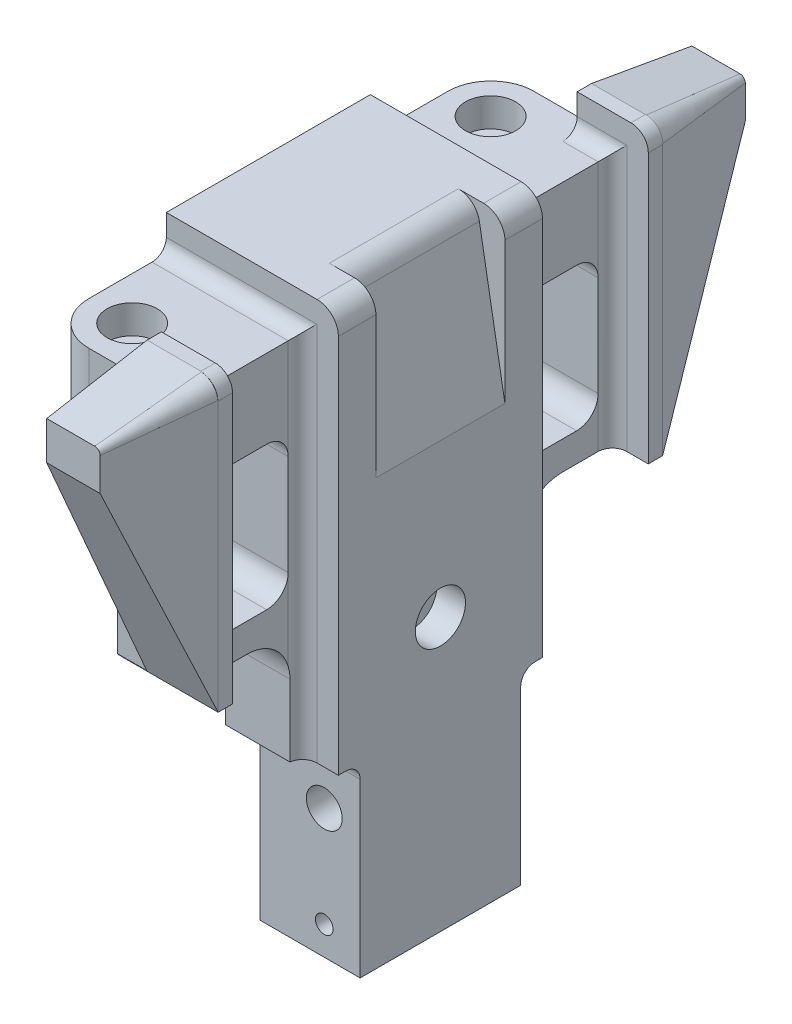
SolidWorks part; units mm, degrees
material "Nylon 101"
ref_plane "Front Plane" through (0, 0, 0) normal (0, 0, 1) x (1, 0, 0)
ref_plane "Top Plane" through (0, 0, 0) normal (0, 1, 0) x (1, 0, 0)
ref_plane "Right Plane" through (0, 0, 0) normal (1, 0, 0) x (0, 0, -1)
sketch "Sketch1" plane through (0, 0, 0) normal (0, 0, 1) x (1, 0, 0)
  line L1 (-19.05, -65.0875) -> (19.05, -65.0875)
  line L2 (-19.05, -65.0875) -> (-19.05, 65.0875)
  line L3 (-19.05, 65.0875) -> (19.05, 65.0875)
  line L4 (19.05, -65.0875) -> (19.05, 65.0875)
  line L5 (-19.05, -65.0875) -> (19.05, 65.0875) construction
  line L6 (-19.05, 65.0875) -> (19.05, -65.0875) construction
  point P0 (0, 0)
  dimension "D1" = 38.1
  dimension "D2" = 130.175
extrude "Boss-Extrude1" add sketch "Sketch1" against normal blind 71.4375
sketch "Sketch2" plane through (19.05, 0, 0) normal (1, 0, 0) x (0, 0, -1)
  line L0 (71.4375, -65.0875) -> (71.4375, 65.0875) construction
  line L1 (71.4375, 1.5875) -> (34.925, 1.5875)
  line L2 (71.4375, 1.5875) -> (71.4375, -65.0875)
  line L3 (71.4375, -65.0875) -> (25.4, -65.0875)
  line L4 (25.4, -7.9375) -> (25.4, -65.0875)
  line L5 (71.4375, -65.0875) -> (0, -65.0875) construction
  line L6 (71.4375, 65.0875) -> (0, 65.0875) construction
  line L7 (0, -65.0875) -> (0, 65.0875) construction
  arc A0 (25.4, -7.9375) -> (34.925, 1.5875) centre (34.925, -7.9375) cw
  dimension "D3" = 9.525
  dimension "D1" = 63.5
  dimension "D2" = 25.4
extrude "Cut-Extrude1" cut sketch "Sketch2" against normal through all
sketch "Sketch3" plane through (19.05, 0, 0) normal (1, 0, 0) x (0, 0, -1)
  line L0 (25.4, -7.9375) -> (25.4, -65.0875) construction
  line L1 (25.4, -23.8125) -> (20.955, -23.8125)
  line L2 (25.4, -23.8125) -> (25.4, -65.0875)
  line L3 (25.4, -65.0875) -> (17.78, -65.0875)
  line L4 (17.78, -26.9875) -> (17.78, -65.0875)
  line L5 (25.4, -65.0875) -> (0, -65.0875) construction
  arc A0 (17.78, -26.9875) -> (20.955, -23.8125) centre (20.955, -26.9875) cw
  point P10 (17.78, -23.8125)
  dimension "D2" = 3.175
  dimension "D1" = 7.62
  dimension "D3" = 41.275
extrude "Cut-Extrude2" cut sketch "Sketch3" against normal through all
sketch "Sketch4" plane through (19.05, 0, 0) normal (1, 0, 0) x (0, 0, -1)
  line L0 (71.4375, 65.0875) -> (0, 65.0875) construction
  line L1 (22.5933, 65.0875) -> (46.0375, 65.0875)
  line L2 (22.5933, 65.0875) -> (22.5933, 60.325)
  line L3 (25.7683, 57.15) -> (42.8625, 57.15)
  line L4 (46.0375, 65.0875) -> (46.0375, 60.325)
  line L7 (71.4375, 1.5875) -> (71.4375, 65.0875) construction
  arc A0 (46.0375, 60.325) -> (42.8625, 57.15) centre (42.8625, 60.325) cw
  arc A1 (25.7683, 57.15) -> (22.5933, 60.325) centre (25.7683, 60.325) cw
  dimension "D4" = 3.175
  dimension "D1" = 25.4
  dimension "D2" = 23.4442
  dimension "D3" = 7.9375
extrude "Cut-Extrude3" cut sketch "Sketch4" against normal through all
sketch "Sketch5" plane through (0, 57.15, 0) normal (0, 1, 0) x (1, 0, 0)
  line L0 (-19.05, 22.5933) -> (19.05, 22.5933) construction
  line L1 (19.05, 46.0375) -> (14.2875, 46.0375)
  line L2 (19.05, 46.0375) -> (19.05, 22.5933)
  line L3 (19.05, 22.5933) -> (14.2875, 22.5933)
  line L4 (11.1125, 42.8625) -> (11.1125, 25.7683)
  arc A0 (14.2875, 22.5933) -> (11.1125, 25.7683) centre (14.2875, 25.7683) cw
  arc A1 (11.1125, 42.8625) -> (14.2875, 46.0375) centre (14.2875, 42.8625) cw
  point P9 (11.1125, 22.5933)
  dimension "D2" = 3.175
  dimension "D1" = 7.9375
extrude "Cut-Extrude5" cut sketch "Sketch5" against normal through all and the other way through all
sketch "Sketch6" plane through (0, 65.0875, 0) normal (0, 1, 0) x (1, 0, 0)
  line L0 (19.05, 71.4375) -> (-19.05, 71.4375) construction
  line L1 (-19.05, 42.8625) -> (3.302, 42.8625)
  line L2 (-19.05, 42.8625) -> (-19.05, 71.4375)
  line L3 (-19.05, 71.4375) -> (3.302, 71.4375)
  line L4 (3.302, 42.8625) -> (3.302, 71.4375)
  line L5 (19.05, 71.4375) -> (19.05, 46.0375) construction
  line L6 (-19.05, 71.4375) -> (-19.05, 46.0375) construction
  line L8 (-19.05, 42.8625) -> (11.1125, 42.8625) construction
  dimension "D1" = 15.748
extrude "Cut-Extrude6" cut sketch "Sketch6" against normal blind 7.9375
sketch "Sketch7" plane through (0, 57.15, 0) normal (0, 1, 0) x (1, 0, 0)
  line L1 (3.302, 71.4375) -> (-19.05, 71.4375)
  line L2 (3.302, 71.4375) -> (3.302, 49.276)
  line L3 (3.302, 49.276) -> (-19.05, 49.276)
  line L4 (-19.05, 71.4375) -> (-19.05, 49.276)
  line L5 (-19.05, 25.7683) -> (-19.05, 71.4375) construction
  dimension "D1" = 22.1615
extrude "Cut-Extrude7" cut sketch "Sketch7" against normal through all
sketch "Sketch8" plane through (0, 65.0875, 0) normal (0, 1, 0) x (1, 0, 0)
  line L0 (15.1311, 71.4375) -> (19.05, 71.4375)
  line L1 (19.05, 71.4375) -> (3.302, 71.4375) construction
  line L2 (19.05, 71.4375) -> (19.05, 49.2125)
  line L3 (19.05, 71.4375) -> (19.05, 46.0375) construction
  line L4 (19.05, 49.2125) -> (15.1311, 71.4375)
  line L5 (3.302, 46.0375) -> (19.05, 46.0375) construction
  dimension "D1" = 10
  dimension "D2" = 3.175
extrude "Cut-Extrude8" cut sketch "Sketch8" against normal through all
fillet "Fillet1" radius 9.525 1 edges at (-19.05, 29.3688, -49.276)
sketch "Sketch9" plane through (0, 0, 0) normal (0, 0, 1) x (1, 0, 0)
  line L0 (12.7, 65.0875) -> (19.05, 65.0875)
  line L1 (19.05, 65.0875) -> (-19.05, 65.0875) construction
  line L2 (19.05, 65.0875) -> (19.05, 29.0749)
  line L3 (19.05, -65.0875) -> (19.05, 65.0875) construction
  line L4 (19.05, 29.0749) -> (12.7, 65.0875)
  dimension "D1" = 10
  dimension "D2" = 6.35
extrude "Cut-Extrude9" cut sketch "Sketch9" against normal blind 14.2875
fillet "Fillet3" radius 4.7307 2 edges at (12.7, 65.0875, -7.1437) (19.05, 65.0875, -18.4404)
sketch "Sketch11" plane through (19.05, 0, 0) normal (1, 0, 0) x (0, 0, -1)
  line L0 (71.4375, 52.6923) -> (71.4375, 1.5875)
  line L1 (71.4375, 1.5875) -> (71.4375, 65.0875) construction
  line L2 (71.4375, 1.5875) -> (49.2125, 1.5875)
  line L3 (71.4375, 1.5875) -> (49.2125, 1.5875) construction
  line L4 (49.2125, 1.5875) -> (71.4375, 52.6923)
  line L5 (14.2875, 65.0875) -> (22.5933, 65.0875) construction
  line L6 (46.0375, 1.5875) -> (46.0375, 65.0875) construction
  dimension "D1" = 12.3952
  dimension "D2" = 3.175
extrude "Cut-Extrude12" cut sketch "Sketch11" against normal through all
sketch "Sketch12" plane through (19.05, 0, 0) normal (1, 0, 0) x (0, 0, -1)
  line L0 (34.925, 1.5875) -> (42.8625, 1.5875) construction
  line L1 (30.5308, 39.6875) -> (38.1, 39.6875)
  line L2 (25.7683, 34.925) -> (25.7683, 12.7)
  line L3 (30.5308, 7.9375) -> (38.1, 7.9375)
  line L4 (42.8625, 34.925) -> (42.8625, 12.7)
  line L5 (42.8625, 57.15) -> (42.8625, 1.5875) construction
  line L6 (25.7683, 57.15) -> (25.7683, -5.3144) construction
  arc A0 (30.5308, 7.9375) -> (25.7683, 12.7) centre (30.5308, 12.7) cw
  arc A1 (38.1, 7.9375) -> (42.8625, 12.7) centre (38.1, 12.7) ccw
  arc A2 (38.1, 39.6875) -> (42.8625, 34.925) centre (38.1, 34.925) cw
  arc A3 (30.5308, 39.6875) -> (25.7683, 34.925) centre (30.5308, 34.925) ccw
  dimension "D3" = 4.7625
  dimension "D1" = 6.35
  dimension "D2" = 38.1
extrude "Cut-Extrude13" cut sketch "Sketch12" against normal through all
sketch "Sketch13" plane through (19.05, 0, 0) normal (1, 0, 0) x (0, 0, -1)
  line L0 (0, -65.0875) -> (0, 29.0749) construction
  line L1 (17.78, -65.0875) -> (0, -65.0875) construction
  point P0 (7.9375, -36.5125)
  point P1 (7.9375, -36.5125)
  dimension "D1" = 7.9375
  dimension "D2" = 28.575
sketch "Sketch18" plane through (0, 0, -17.78) normal (0, 0, -1) x (-1, 0, 0)
  line L0 (-19.05, -26.9875) -> (-19.05, -65.0875) construction
  line L1 (19.05, -65.0875) -> (-19.05, -65.0875) construction
  point P0 (-11.1125, -36.5125)
  dimension "D1" = 7.9375
  dimension "D2" = 28.575
hole_wizard "5/16 (0.3125) Diameter Hole2" positions "3DSketch2" profile "Sketch19" hole size "5/16" standard "ANSI Inch"
sketch3d "3DSketch2"
  point P0 (11.1125, -36.5125, -17.78)
sketch "Sketch19" plane through (11.1125, -36.5125, -17.78) normal (1, 0, 0) x (0, 1, 0)
  line L0 (0, 0) -> (0, 14.0687)
  line L1 (0, 14.0687) -> (3.9687, 11.684)
  line L2 (3.9687, 11.684) -> (3.9687, 0)
  line L5 (3.9687, 0) -> (0, 0)
  line L10 (0, 14.0687) -> (-3.9688, 11.684) construction
  line L11 (0, -6.35) -> (0, 107.95) construction
  dimension "Hole Dia." = 7.9375
  dimension "Hole Depth" = 11.684
  dimension "Drill Angle" = 118
sketch "Sketch20" plane through (0, 0, -17.78) normal (0, 0, -1) x (-1, 0, 0)
  line L0 (-19.05, -26.9875) -> (-19.05, -65.0875) construction
  line L1 (19.05, -65.0875) -> (-19.05, -65.0875) construction
  point P0 (-11.1125, -58.7375)
  dimension "D1" = 7.9375
  dimension "D2" = 6.35
hole_wizard "#23 (0.154) Diameter Hole2" positions "3DSketch3" profile "Sketch21" hole size "#23" standard "ANSI Inch"
sketch3d "3DSketch3"
  point P0 (11.1125, -58.7375, -17.78)
sketch "Sketch21" plane through (11.1125, -58.7375, -17.78) normal (1, 0, 0) x (0, 1, 0)
  line L0 (0, 0) -> (0, 12.8592)
  line L1 (0, 12.8592) -> (1.9558, 11.684)
  line L2 (1.9558, 11.684) -> (1.9558, 0)
  line L5 (1.9558, 0) -> (0, 0)
  line L10 (0, 12.8592) -> (-1.9558, 11.684) construction
  line L11 (0, -6.35) -> (0, 107.95) construction
  dimension "Hole Dia." = 3.9116
  dimension "Hole Depth" = 11.684
  dimension "Drill Angle" = 118
sketch "Sketch22" plane through (-19.05, 0, 0) normal (-1, 0, 0) x (0, 0, 1)
  line L0 (-17.78, -65.0875) -> (0, -65.0875) construction
  line L1 (-17.78, -26.9875) -> (-17.78, -65.0875) construction
  point P0 (-11.43, -36.5125)
  point P1 (-11.43, -58.7375)
  dimension "D1" = 28.575
  dimension "D2" = 6.35
  dimension "D3" = 6.35
hole_wizard "#8-32 Tapped Hole1" positions "3DSketch4" profile "Sketch23" tap size "#8-32" standard "ANSI Inch" end condition up to next
sketch3d "3DSketch4"
  point P0 (-19.05, -36.5125, -11.43)
  point P3 (-19.05, -58.7375, -11.43)
sketch "Sketch23" plane through (-19.05, -36.5125, -11.43) normal (0, 1, 0) x (0, 0, 1)
  line L0 (0, 0) -> (0, 26.1938)
  line L1 (0, 26.1938) -> (1.7272, 26.1938)
  line L2 (1.7272, 26.1938) -> (1.7272, 0)
  line L5 (1.7272, 0) -> (0, 0)
  line L11 (0, -6.35) -> (0, 107.95) construction
  dimension "Thru Tap Drill Dia." = 3.4544
  dimension "Thru Tap Drill Depth" = 26.1938
cosmetic thread "Hole Thread1" parameters "D1"=29.2449, "D2"=4.1656
cosmetic thread "Hole Thread2" parameters "D1"=29.2449, "D2"=4.1656
sketch "Sketch26" plane through (0, 0, 0) normal (0, 0, 1) x (1, 0, 0)
  line L0 (-19.05, 65.0875) -> (-19.05, -65.0875) construction
  line L1 (-19.05, 39.6875) -> (0, 39.6875)
  line L2 (-19.05, 39.6875) -> (-19.05, -65.0875)
  line L3 (-19.05, -65.0875) -> (-3.175, -65.0875)
  line L4 (-3.175, 33.0835) -> (-3.175, -65.0875)
  line L6 (-19.05, -65.0875) -> (19.05, -65.0875) construction
  line L10 (-3.175, 33.0835) -> (0, 33.0835)
  line L11 (3.175, 36.5125) -> (3.175, 36.2585)
  arc A0 (3.175, 36.2585) -> (0, 33.0835) centre (0, 36.2585) cw
  arc A1 (3.175, 36.5125) -> (0, 39.6875) centre (0, 36.5125) ccw
  dimension "D3" = 3.175
  dimension "D1" = 15.875
  dimension "D2" = 98.171
  dimension "D4" = 6.35
  dimension "D5" = 0.254
  dimension "D6" = 3.175
extrude "Cut-Extrude14" cut sketch "Sketch26" against normal through all
sketch3d "3DSketch6" plane through (0, 0, 0) normal (0, 0, 1) x (1, 0, 0)
sketch "Sketch27" plane through (0, 0, -49.276) normal (0, 0, 1) x (1, 0, 0)
  line L0 (19.05, 1.5875) -> (19.05, 65.0875) construction
  line L1 (19.05, 65.0875) -> (15.0813, 65.0875)
  line L2 (19.05, 65.0875) -> (19.05, 61.1188)
  arc A0 (15.0813, 65.0875) -> (19.05, 61.1188) centre (15.0813, 61.1188) cw
  dimension "D1" = 3.9688
sketch "Sketch28" plane through (19.05, 0, 0) normal (1, 0, 0) x (0, 0, -1)
  line L0 (71.4375, 65.0875) -> (71.4375, 61.1686)
  line L1 (71.4375, 52.6923) -> (71.4375, 65.0875) construction
  line L2 (71.4375, 61.1686) -> (49.2125, 65.0875)
  line L3 (71.4375, 65.0875) -> (49.2125, 65.0875) construction
  line L4 (49.2125, 65.0875) -> (71.4375, 65.0875)
  dimension "D1" = 22.225
  dimension "D2" = 10
extrude "Cut-Extrude15" cut sketch "Sketch28" against normal through all
sketch "Sketch29" plane through (0, 0, -71.4375) normal (0, 0, -1) x (-1, 0, 0)
  line L0 (-15.1311, 59.9748) -> (-15.1311, 61.1686)
  line L1 (-15.1311, 52.6923) -> (-15.1311, 61.1686) construction
  line L2 (-15.1311, 61.1686) -> (-13.9373, 61.1686)
  line L3 (-3.302, 61.1686) -> (-15.1311, 61.1686) construction
  arc A0 (-13.9373, 61.1686) -> (-15.1311, 59.9748) centre (-13.9373, 59.9748) ccw
  dimension "D1" = 1.1938
loft "Cut-Loft3" cut profiles "Sketch29", "Sketch27"
fillet "Fillet5" radius 3.8354 1 edges at (19.05, 65.0875, -47.625)
sketch "Sketch30" plane through (0, 57.15, 0) normal (0, 1, 0) x (1, 0, 0)
  line L0 (-19.05, 25.7683) -> (-19.05, 39.751) construction
  line L1 (3.302, 71.4375) -> (13.9373, 71.4375) construction
  point P0 (-9.525, 39.6875)
  dimension "D1" = 9.525
  dimension "D2" = 31.75
hole_wizard "CBORE for 1/4 Socket Head Cap Screw1" positions "3DSketch7" profile "Sketch31" counterbore size "1/4" standard "ANSI Inch" end condition through all
sketch3d "3DSketch7"
  point P0 (-9.525, 57.15, -39.6875)
sketch "Sketch31" plane through (-9.525, 57.15, -39.6875) normal (1, 0, 0) x (0, 0, 1)
  line L0 (0, 0) -> (0, 122.2375)
  line L1 (0, 122.2375) -> (3.3782, 122.2375)
  line L3 (3.3782, 122.2375) -> (3.3782, 6.35)
  line L4 (3.3782, 6.35) -> (5.5562, 6.35)
  line L5 (5.5562, 6.35) -> (5.5562, 0)
  line L7 (5.5562, 0) -> (0, 0)
  line L11 (0, -6.35) -> (0, 107.95) construction
  dimension "Thru Hole Dia." = 6.7564
  dimension "Thru Hole Depth" = 122.2375
  dimension "C'Bore Dia." = 11.1125
  dimension "C'Bore Depth" = 6.35
mirror "Mirror1" about plane through (0, 0, 0) normal (0, 0, -1) of bodies 124
sketch "Sketch32" plane through (19.05, 0, 0) normal (1, 0, 0) x (0, 0, -1)
  line L0 (-14.2875, 65.0875) -> (-22.5933, 65.0875) construction
  point P0 (0, -4.7625)
  dimension "D1" = 69.85
hole_wizard "CBORE for 1/4 Socket Head Cap Screw2" positions "3DSketch8" profile "Sketch33" counterbore size "1/4" standard "ANSI Inch" end condition through all
sketch3d "3DSketch8"
  point P0 (19.05, -4.7625, 0)
sketch "Sketch33" plane through (19.05, -4.7625, 0) normal (0, 1, 0) x (0, 0, -1)
  line L0 (0, 0) -> (0, 38.1)
  line L1 (0, 38.1) -> (3.3782, 38.1)
  line L3 (3.3782, 38.1) -> (3.3782, 6.35)
  line L4 (3.3782, 6.35) -> (5.5562, 6.35)
  line L5 (5.5562, 6.35) -> (5.5562, 0)
  line L7 (5.5562, 0) -> (0, 0)
  line L11 (0, -6.35) -> (0, 107.95) construction
  dimension "Thru Hole Dia." = 6.7564
  dimension "Thru Hole Depth" = 38.1
  dimension "C'Bore Dia." = 11.1125
  dimension "C'Bore Depth" = 6.35
